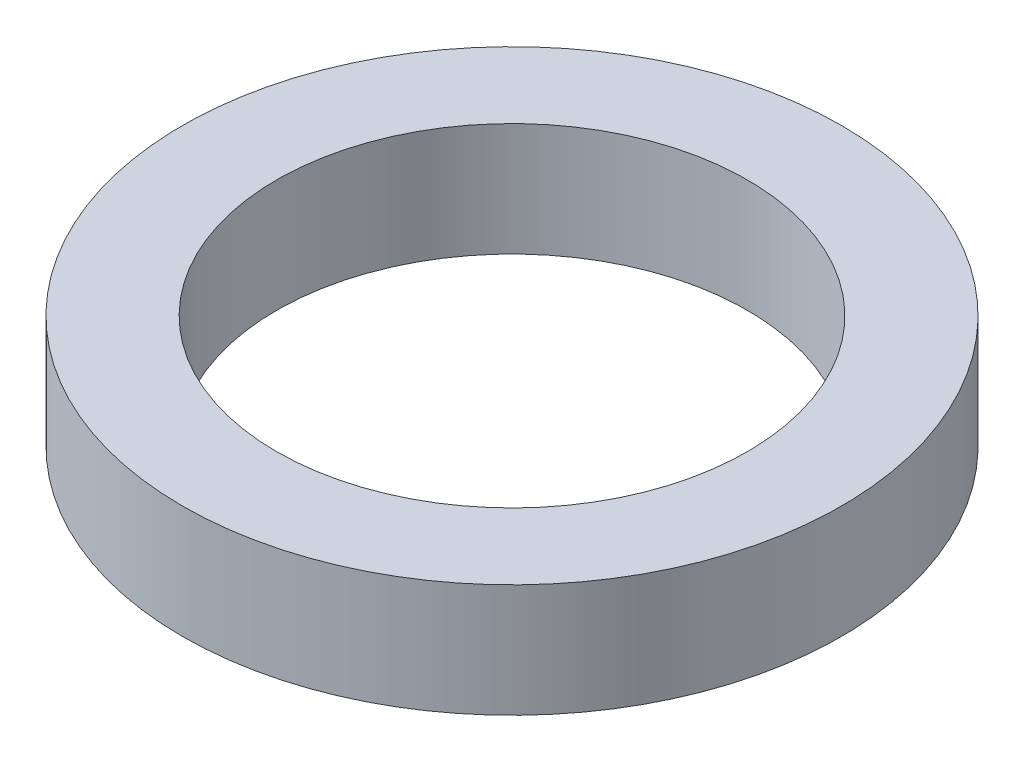
SolidWorks part; units mm, degrees
ref_plane "Front Plane" through (0, 0, 0) normal (0, 0, 1) x (1, 0, 0)
ref_plane "Top Plane" through (0, 0, 0) normal (0, 1, 0) x (1, 0, 0)
ref_plane "Right Plane" through (0, 0, 0) normal (1, 0, 0) x (0, 0, -1)
sketch "Sketch1" plane through (0, 0, 0) normal (0, 1, 0) x (1, 0, 0)
  circle A0 centre (0, 0) radius 70
  dimension "FLANGE_OD" = 140
extrude "Boss-Extrude1" add sketch "Sketch1" along normal blind 24
sketch "Sketch2" plane through (0, 0, 0) normal (0, 1, 0) x (1, 0, 0)
  circle A0 centre (0, 0) radius 50
  dimension "BORE_D" = 100
extrude "Cut-Extrude1" cut sketch "Sketch2" along normal through all
sketch "Sketch3" plane through (0, 24, 0) normal (0, 1, 0) x (1, 0, 0)
  circle A0 centre (0, 0) radius 31.4309 construction
  circle A1 centre (-31.4309, 0) radius 3.5474
  dimension "BOLT_D" = 7.0948
  dimension "BOLT_PCD" = 62.8617
extrude "Cut-Extrude2" cut sketch "Sketch3" against normal blind 21.7179 rebuild error yes
pattern_circular "CirPattern1" count 4 over 360 rebuild error yes
